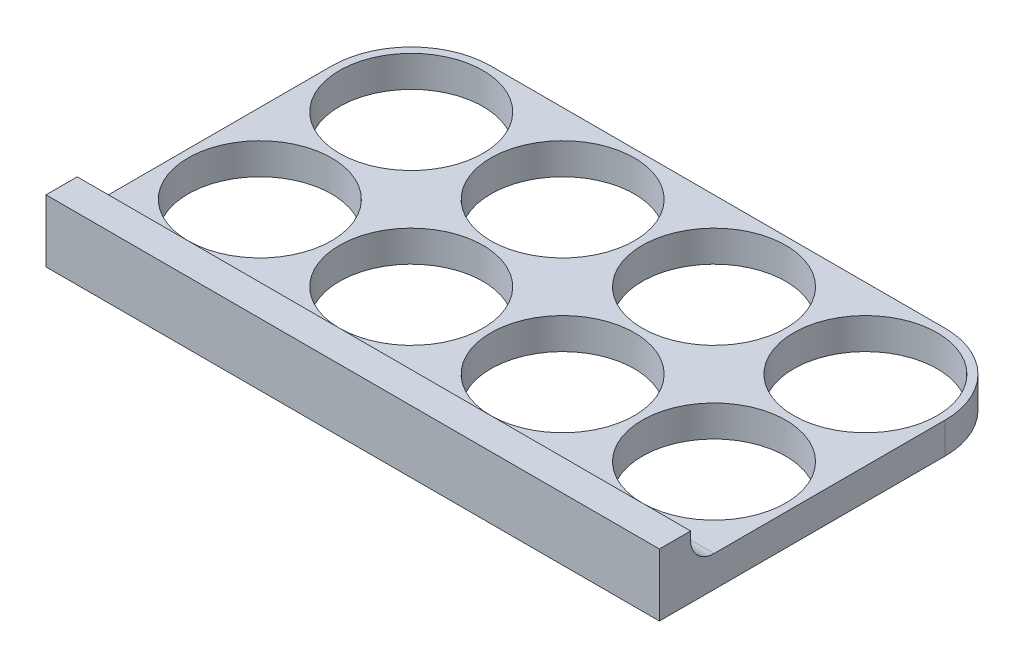
SolidWorks part; units mm, degrees
ref_plane "Front Plane" through (0, 0, 0) normal (0, 0, 1) x (1, 0, 0)
ref_plane "Top Plane" through (0, 0, 0) normal (0, 1, 0) x (1, 0, 0)
ref_plane "Right Plane" through (0, 0, 0) normal (1, 0, 0) x (0, 0, -1)
sketch "Sketch1" plane through (0, 0, 0) normal (0, 1, 0) x (1, 0, 0)
  line L0 (0, 0) -> (58.2, 0) construction
  line L1 (0, 19.4) -> (58.2, 19.4) construction
  line L2 (0, 0) -> (58.2, 19.4) construction
  line L3 (-10.2, 0) -> (-10.2, -17.2)
  line L5 (-10.2, 0) -> (-10.2, 19.4)
  line L6 (0, 29.6) -> (58.2, 29.6)
  line L7 (68.4, 0) -> (68.4, 19.4)
  line L8 (29.1, 29.6) -> (29.1, -9.2) construction
  line L9 (-10.2, 9.7) -> (68.4, 9.7) construction
  line L10 (-10.2, -17.2) -> (68.4, -17.2)
  line L11 (68.4, -17.2) -> (68.4, 0)
  line L12 (0, -9.2) -> (58.2, -9.2) construction
  circle A0 centre (0, 0) radius 9.2
  circle A1 centre (19.4, 0) radius 9.2
  circle A2 centre (38.8, 0) radius 9.2
  circle A3 centre (58.2, 0) radius 9.2
  circle A4 centre (19.4, 19.4) radius 9.2
  circle A5 centre (38.8, 19.4) radius 9.2
  circle A6 centre (58.2, 19.4) radius 9.2
  circle A7 centre (0, 19.4) radius 9.2
  arc A10 (58.2, 29.6) -> (68.4, 19.4) centre (58.2, 19.4) cw
  arc A11 (-10.2, 19.4) -> (0, 29.6) centre (0, 19.4) cw
  point P3 (29.1, 9.7)
  point P4 (29.1, 9.7)
  point P22 (0, 28.6)
  point P25 (68.4, -10.2)
  point P31 (68.4, 29.6)
  point P34 (-10.2, 29.6)
  dimension "D1" = 18.4
  dimension "D2" = 4
  dimension "D4" = 19.4
  dimension "D5" = 19.4
  dimension "D6" = 19.4
  dimension "D8" = 78.6
  dimension "D10" = 8
  dimension "D3" = 2
extrude "Boss-Extrude1" add sketch "Sketch1" along normal blind 4
sketch "Sketch2" plane through (0, 4, 0) normal (0, 1, 0) x (1, 0, 0)
  line L0 (68.4, -17.2) -> (68.4, 19.4) construction
  line L1 (-10.2, -17.2) -> (68.4, -17.2)
  line L2 (-10.2, -17.2) -> (-10.2, -13.2)
  line L3 (-10.2, -13.2) -> (68.4, -13.2)
  line L4 (68.4, -17.2) -> (68.4, -13.2)
  dimension "D1" = 4
extrude "Boss-Extrude2" add sketch "Sketch2" along normal blind 4
ref_plane "Plane1" through (29.1, 0, 0) normal (1, 0, 0) x (0, 0, -1)
fillet "Fillet1" radius 3 1 edges at (29.1, 4, 13.2)
